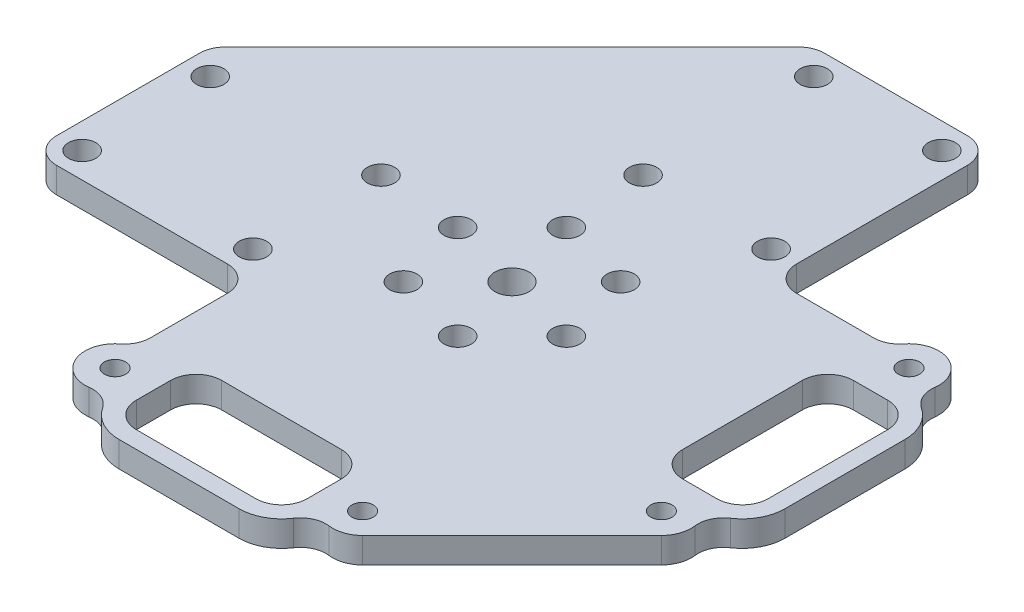
SolidWorks part; units mm, degrees
material "6061-T6 (SS)"
ref_plane "Front Plane" through (0, 0, 0) normal (0, 0, 1) x (1, 0, 0)
ref_plane "Top Plane" through (0, 0, 0) normal (0, 1, 0) x (1, 0, 0)
ref_plane "Right Plane" through (0, 0, 0) normal (1, 0, 0) x (0, 0, -1)
sketch "Sketch1" plane through (0, 0, 0) normal (0, 1, 0) x (1, 0, 0)
  line L0 (-14.5, -32) -> (14.5, -32) construction
  line L1 (11.85, 18.5) -> (-3.15, 18.5)
  line L2 (11.85, 18.5) -> (11.85, 38.5)
  line L3 (11.85, 38.5) -> (-3.15, 38.5)
  line L4 (-3.15, 18.5) -> (-3.15, 38.5)
  line L5 (11.85, 18.5) -> (-3.15, 38.5) construction
  line L6 (11.85, 38.5) -> (-3.15, 18.5) construction
  line L7 (-18.5, -11.85) -> (-38.5, -11.85)
  line L8 (-18.5, -11.85) -> (-18.5, 3.15)
  line L9 (-18.5, 3.15) -> (-38.5, 3.15)
  line L10 (-38.5, -11.85) -> (-38.5, 3.15)
  line L11 (-18.5, -11.85) -> (-38.5, 3.15) construction
  line L12 (-18.5, 3.15) -> (-38.5, -11.85) construction
  line L13 (21.7, 15) -> (-13, 15)
  line L14 (21.7, 15) -> (21.7, 42)
  line L15 (21.7, 42) -> (-13, 42)
  line L16 (-13, 15) -> (-13, 42)
  line L17 (21.7, 15) -> (-13, 42) construction
  line L18 (21.7, 42) -> (-13, 15) construction
  line L19 (-15, -21.7) -> (-42, -21.7)
  line L20 (-15, -21.7) -> (-15, 13)
  line L21 (-15, 13) -> (-42, 13)
  line L22 (-42, -21.7) -> (-42, 13)
  line L23 (-15, -21.7) -> (-42, 13) construction
  line L24 (-15, 13) -> (-42, -21.7) construction
  line L25 (10, -37) -> (-10, -37)
  line L26 (10, -37) -> (10, -27)
  line L27 (10, -27) -> (-10, -27)
  line L28 (-10, -37) -> (-10, -27)
  line L29 (10, -37) -> (-10, -27) construction
  line L30 (10, -27) -> (-10, -37) construction
  line L31 (37, -10) -> (27, -10)
  line L32 (37, -10) -> (37, 10)
  line L33 (37, 10) -> (27, 10)
  line L34 (27, -10) -> (27, 10)
  line L35 (37, -10) -> (27, 10) construction
  line L36 (37, 10) -> (27, -10) construction
  line L37 (32, 14.5) -> (32, -14.5) construction
  circle A0 centre (0, 0) radius 2
  circle A1 centre (0, 0) radius 9
  circle A2 centre (0, 0) radius 12.7
  point P3 (4.35, 28.5)
  point P8 (-28.5, -4.35)
  point P15 (0, -32)
  point P16 (-28.5, -4.35)
  point P17 (4.35, 28.5)
  point P30 (32, 0)
  point P38 (0, -32)
  point P41 (32, 0)
  dimension "D1" = 4
  dimension "D4" = 18
  dimension "D11" = 25.4
  dimension "D2" = 20
  dimension "D3" = 15
  dimension "D5" = 34.7
  dimension "D6" = 27
  dimension "D7" = 2
  dimension "D8" = 2
  dimension "D9" = 15
  dimension "D10" = 15
  dimension "D12" = 32
  dimension "D13" = 10
  dimension "D14" = 20
  dimension "D15" = 32
  dimension "D16" = 4.5
sketch "Sketch2" plane through (0, 0, 0) normal (0, 1, 0) x (1, 0, 0)
  line L3 (-15.5, -14.85) -> (-41.5, -14.85)
  line L4 (-41.5, -14.85) -> (-41.5, 6.15)
  line L5 (-41.5, 6.15) -> (-23.825, 23.825)
  line L6 (-18.5, -11.85) -> (-38.5, -11.85) construction
  line L9 (-38.5, -11.85) -> (-38.5, 3.15) construction
  line L10 (-18.5, -11.85) -> (-18.5, 3.15) construction
  line L12 (-18.5, 3.15) -> (-38.5, 3.15) construction
  line L16 (-15.5, -14.85) -> (-15.5, -28.6459)
  line L22 (16.9749, -34.4749) -> (25.7249, -25.7249)
  line L29 (25.7249, -25.7249) -> (-23.825, 23.825)
  line L39 (12, -27) -> (12, -39)
  line L40 (12, -39) -> (-12, -39)
  line L41 (-12, -39) -> (-12, -27)
  line L42 (12, -34.4495) -> (12, -39)
  line L43 (12, -39) -> (-12, -39)
  line L44 (-12, -39) -> (-12, -34.4495)
  arc A0 (-15.5, -28.6459) -> (-12, -34.4495) centre (-14.5, -32) ccw
  arc A2 (12, -34.4495) -> (16.9749, -34.4749) centre (14.5, -32) ccw
  dimension "D1" = 7
  dimension "D2" = 3
  dimension "D3" = 45
  dimension "D4" = 2
  dimension "D5" = 3
  dimension "D6" = 3
  dimension "D8" = 3
extrude "Boss-Extrude1" add sketch "Sketch2" along normal blind 3
mirror "Mirror5" about plane through (25.7249, 3, 25.7249) normal (-0.7071, 0, 0.7071) of bodies 101
hole_wizard "M3 Clearance Hole1" positions "Sketch3" profile "Sketch4" hole size "M3" standard "ANSI Metric" end condition up to next
sketch "Sketch3" plane through (0, 3, 0) normal (0, 1, 0) x (1, 0, 0)
  point P0 (-38.5, 3.15)
  point P3 (-18.5, 3.15)
  point P6 (-18.5, -11.85)
  point P9 (-38.5, -11.85)
  point P12 (-3.15, 18.5)
  point P15 (-3.15, 38.5)
  point P18 (11.85, 38.5)
  point P21 (11.85, 18.5)
sketch "Sketch4" plane through (-38.5, 3, -3.15) normal (1, 0, 0) x (0, 0, 1)
  line L0 (0, 0) -> (0, 3)
  line L1 (0, 3) -> (1.6, 3)
  line L2 (1.6, 3) -> (1.6, 0)
  line L5 (1.6, 0) -> (0, 0)
  line L11 (0, -6.35) -> (0, 107.95) construction
  dimension "Thru Hole Dia." = 3.2
  dimension "Thru Hole Depth" = 3
hole_wizard "M3 Clearance Hole2" positions "Sketch5" profile "Sketch6" hole size "M3" standard "ANSI Metric" end condition up to next
sketch "Sketch5" plane through (0, 3, 0) normal (0, 1, 0) x (1, 0, 0)
  line L4 (-8.6933, 2.3294) -> (-2.3294, 8.6933) construction
  line L5 (0, 0) -> (-5.5114, 5.5114) construction
  line L7 (-1000, 0) -> (49000, 0) construction
  circle A0 centre (0, 0) radius 9 construction
  point P23 (-2.3294, 8.6933)
  point P46 (6.364, 6.364)
  point P47 (8.6933, -2.3294)
  point P48 (2.3294, -8.6933)
  point P49 (-6.364, -6.364)
  point P50 (-8.6933, 2.3294)
  dimension "D1" = 45
  dimension "D2" = 6
sketch "Sketch6" plane through (-2.3294, 3, -8.6933) normal (1, 0, 0) x (0, 0, 1)
  line L0 (0, 0) -> (0, 3)
  line L1 (0, 3) -> (1.6, 3)
  line L2 (1.6, 3) -> (1.6, 0)
  line L5 (1.6, 0) -> (0, 0)
  line L11 (0, -6.35) -> (0, 107.95) construction
  dimension "Thru Hole Dia." = 3.2
  dimension "Thru Hole Depth" = 3
hole_wizard "Ø4.0 (4) Diameter Hole1" positions "Sketch7" profile "Sketch8" hole size "Ø4.0" standard "ANSI Metric" end condition up to next
sketch "Sketch7" plane through (0, 3, 0) normal (0, 1, 0) x (1, 0, 0)
  point P0 (0, 0)
sketch "Sketch8" plane through (0, 3, 0) normal (1, 0, 0) x (0, 0, 1)
  line L0 (0, 0) -> (0, 3)
  line L1 (0, 3) -> (2, 3)
  line L2 (2, 3) -> (2, 0)
  line L5 (2, 0) -> (0, 0)
  line L11 (0, -6.35) -> (0, 107.95) construction
  dimension "Thru Hole Dia." = 4
  dimension "Thru Hole Depth" = 3
hole_wizard "Tap Drill for M3x0.5 Tap1" positions "Sketch10" profile "Sketch11" hole size "M3x0.5" standard "ANSI Metric" end condition up to next
sketch "Sketch10" plane through (0, 0, 0) normal (0, -1, 0) x (-1, 0, 0)
  point P0 (-14.5, -32)
  point P3 (14.5, -32)
  point P6 (-32, -14.5)
  point P9 (-32, 14.5)
sketch "Sketch11" plane through (14.5, 0, 32) normal (1, 0, 0) x (0, 0, -1)
  line L0 (0, 0) -> (0, 3)
  line L1 (0, 3) -> (1.25, 3)
  line L2 (1.25, 3) -> (1.25, 0)
  line L5 (1.25, 0) -> (0, 0)
  line L11 (0, -6.35) -> (0, 107.95) construction
  dimension "Thru Hole Dia." = 2.5
  dimension "Thru Hole Depth" = 3
sketch "Sketch9" plane through (0, 3, 0) normal (0, 1, 0) x (1, 0, 0)
  line L0 (27, -10) -> (27, 10) construction
  line L1 (37, 10) -> (27, 10) construction
  line L2 (37, -10) -> (37, 10) construction
  line L3 (37, -10) -> (27, -10) construction
  line L4 (10, -27) -> (-10, -27) construction
  line L5 (10, -37) -> (10, -27) construction
  line L6 (10, -37) -> (-10, -37) construction
  line L7 (-10, -37) -> (-10, -27) construction
  line L8 (27, -10) -> (27, 10)
  line L9 (37, 10) -> (27, 10)
  line L10 (37, -10) -> (37, 10)
  line L11 (37, -10) -> (27, -10)
  line L12 (10, -27) -> (-10, -27)
  line L13 (10, -37) -> (10, -27)
  line L14 (10, -37) -> (-10, -37)
  line L15 (-10, -37) -> (-10, -27)
extrude "Cut-Extrude1" cut sketch "Sketch9" against normal up to surface (3 mm away) up to face at (0, 0, 2)
fillet "Fillet1" radius 3 8 edges at (37, 1.5, -10) (37, 1.5, 10) (27, 1.5, 10) (27, 1.5, -10) (-10, 1.5, 37) (10, 1.5, 37) (10, 1.5, 27) (-10, 1.5, 27)
fillet "Fillet2" radius 5 4 edges at (39, 1.5, -12) (39, 1.5, 12) (12, 1.5, 39) (-12, 1.5, 39)
fillet "Fillet3" radius 3 12 edges at (34.4495, 1.5, 12) (12, 1.5, 34.4495) (-12, 1.5, 34.4495) (-15.5, 1.5, 28.6459) (-15.5, 1.5, 14.85) (-41.5, 1.5, -6.15) (-6.15, 1.5, -41.5) (14.85, 1.5, -41.5) (14.85, 1.5, -15.5) (28.6459, 1.5, -15.5) (34.4495, 1.5, -12) (-41.5, 1.5, 14.85)
